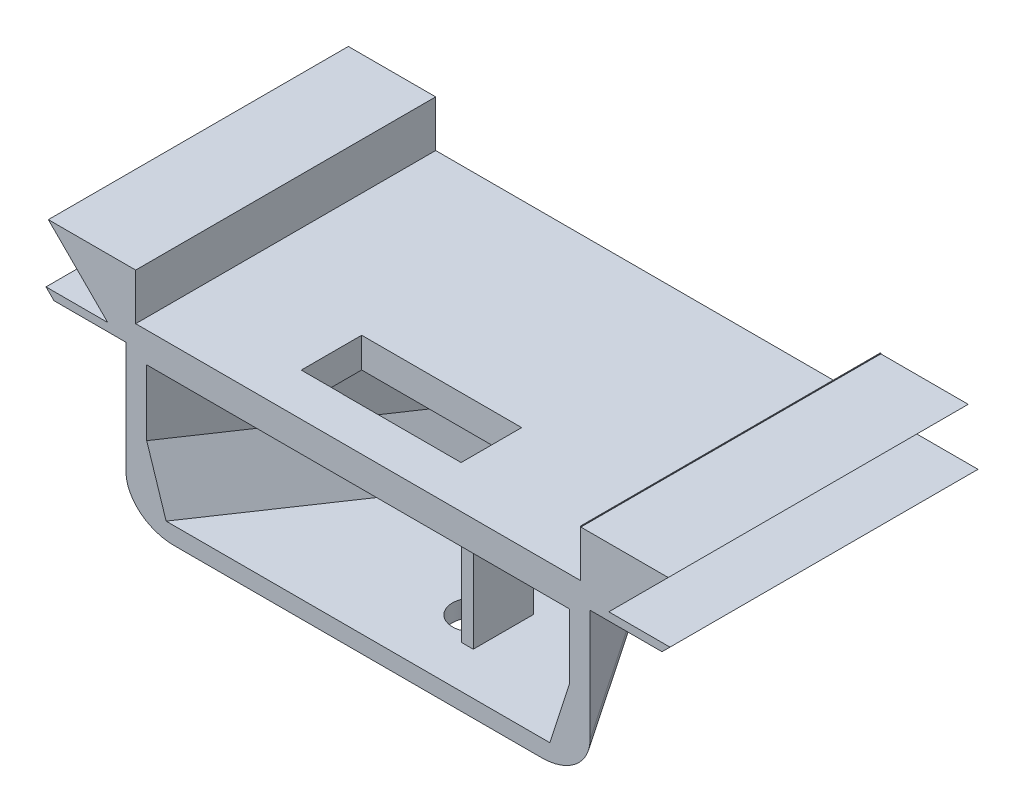
SolidWorks part; units mm, degrees
other "Camera1"
ref_plane "Front Plane" through (0, 0, 0) normal (0, 0, 1) x (1, 0, 0)
ref_plane "Top Plane" through (0, 0, 0) normal (0, 1, 0) x (1, 0, 0)
ref_plane "Right Plane" through (0, 0, 0) normal (1, 0, 0) x (0, 0, -1)
sketch "Sketch1" plane through (0, 0, 0) normal (0, 1, 0) x (1, 0, 0)
  line L0 (0, 0) -> (-116, 0)
  line L1 (-116, 0) -> (-75.5008, 60)
  line L2 (-75.5008, 60) -> (-40.5008, 60)
  line L3 (-40.5008, 60) -> (0, 0)
  dimension "D1" = 60
  dimension "D2" = 116
  dimension "D3" = 35
  dimension "D5" = 72.39
  dimension "D6" = 72.3891
extrude "Boss-Extrude1" add sketch "Sketch1" against normal blind 40
shell "Shell1" thickness 4.2918 removed face at (-58, -20, 0)
chamfer "Chamfer3" distance 15 angle 15 2 edges at (-92.0209, -35.7082, -27.8541) (-23.9799, -35.7082, -27.8541) first distance on face at (-92.0209, -20, -27.8541) first distance on face at (-23.9799, -20, -27.8541)
fillet "Fillet1" radius 10 2 edges at (-20.2504, -40, -30) (-95.7504, -40, -30)
fillet "Fillet2" radius 5 5 edges at (-40.5008, -15, -60) (-44.0345, -37.0711, -60) (-75.5008, -15, -60) (-71.9671, -37.0711, -60) (-58.0008, -40, -60)
sketch "Sketch12" plane through (0, -40, 0) normal (0, -1, 0) x (-1, 0, 0)
  circle A0 centre (47.2824, 18.1003) radius 5.2
sketch "Sketch13" plane through (0, -4.2918, 0) normal (0, -1, 0) x (1, 0, 0)
  line L1 (-39.8423, -25.7584) -> (-42.8423, -25.7584)
  line L2 (-39.8423, -25.7584) -> (-39.8423, -10.6584)
  line L3 (-39.8423, -10.6584) -> (-42.8423, -10.6584)
  line L4 (-42.8423, -25.7584) -> (-42.8423, -10.6584)
  dimension "D1" = 3
extrude "Boss-Extrude3" add sketch "Sketch13" along normal blind 35
extrude "Cut-Extrude12" cut sketch "Sketch12" against normal blind 9
sketch "Sketch15" plane through (0, 0, 0) normal (0, 1, 0) x (1, 0, 0)
  line L8 (-136, 75) -> (20, 75)
  line L9 (20, 0) -> (20, 75)
  line L10 (20, 0) -> (-136, 0)
  line L11 (-136, 0) -> (-136, 75)
extrude "Boss-Extrude7" add sketch "Sketch15" along normal blind 15
sketch "Sketch16" plane through (0, 0, 0) normal (0, 0, 1) x (1, 0, 0)
  line L1 (20.1, 15.2414) -> (20.1, -0.1)
  line L3 (20.1, -0.1) -> (4.7586, -0.1)
  line L6 (4.7586, -0.1) -> (20.1, 15.2414)
  line L8 (20, 15) -> (20, 0) construction
  line L9 (20, 0) -> (5, 0) construction
  line L10 (0, 0) -> (20, 0) construction
  line L11 (5, 0) -> (20, 15) construction
  dimension "D1" = 15
  dimension "D2" = 0.1
extrude "Cut-Extrude14" cut sketch "Sketch16" against normal blind 75
sketch "Sketch17" plane through (0, 0, 0) normal (0, 0, 1) x (1, 0, 0)
  line L0 (-136, 15) -> (-136, 0) construction
  line L1 (-136, 0) -> (-121, 0) construction
  line L2 (-136, 0) -> (-116, 0) construction
  line L3 (-121, 0) -> (-136, 15) construction
  line L4 (-120.5172, -0.2) -> (-136.2, 15.4828)
  line L5 (-136.2, 15.4828) -> (-136.2, -0.2)
  line L6 (-136.2, -0.2) -> (-120.5172, -0.2)
  dimension "D1" = 0.2
extrude "Cut-Extrude15" cut sketch "Sketch17" against normal blind 75
sketch "Sketch18" plane through (0, 0, 0) normal (0, -1, 0) x (1, 0, 0)
  line L0 (-116, 0) -> (-121, 0)
  line L1 (-121, 0) -> (-136.0045, 0)
  line L2 (-136.0045, 0) -> (-136.0045, -75)
  line L5 (20.0045, -75) -> (20.0045, 0)
  line L6 (20.0045, 0) -> (-116, 0)
  line L9 (-136.0045, -75) -> (-136.0045, -77)
  line L10 (20.0045, -75) -> (20.0045, -77)
  line L11 (20.0045, -77) -> (-136.0045, -77)
  dimension "D1" = 75
extrude "Boss-Extrude8" add sketch "Sketch18" along normal blind 2 contours L5 L6 L0 L1 L2 L9 L11 L10
sketch "Sketch20" plane through (0, -2, 0) normal (0, -1, 0) x (-1, 0, 0)
  line L1 (42.8423, 25.7218) -> (72.8207, 25.7218)
  line L2 (42.8423, 25.7218) -> (42.8423, 10.6218)
  line L3 (42.8423, 10.6218) -> (72.8207, 10.6218)
  line L4 (72.8207, 25.7218) -> (72.8207, 10.6218)
extrude "Cut-Extrude17" cut sketch "Sketch20" against normal blind 39 contours L2 L1 L4 L3
sketch "Sketch21" plane through (0, 0, 0) normal (0, 0, 1) x (1, 0, 0)
  line L6 (-135.7172, 15) -> (19.8586, 15) construction
  line L7 (-2.413, 15) -> (-113.583, 15)
  line L9 (-2.413, 15) -> (-113.583, 15)
  line L11 (-2.413, 15) -> (-2.413, 3.2309)
  line L12 (-2.413, 3.2309) -> (-113.583, 3.2309)
  line L13 (-113.583, 15) -> (-113.583, 3.2309)
extrude "Cut-Extrude18" cut sketch "Sketch21" against normal blind 80 contours L11 L9 L13 L12
sketch "Sketch22" plane through (-42.8423, 0, 0) normal (-1, 0, 0) x (0, 0, 1)
  line L1 (-10.6584, -35.7082) -> (-18.2084, -35.7082)
  line L2 (-10.6584, -35.7082) -> (-10.6584, -10.7935)
  line L3 (-10.6584, -10.7935) -> (-18.2084, -10.7935)
  line L4 (-18.2084, -35.7082) -> (-18.2084, -10.7935)
  circle A0 centre (-18.2084, -10.7935) radius 2.4
  dimension "D1" = 4.8
extrude "Cut-Extrude19" cut sketch "Sketch22" against normal blind 10 contours A0
sketch "Sketch27" plane through (0, -4.2918, 0) normal (0, -1, 0) x (-1, 0, 0)
  line L1 (42.8423, 10.6584) -> (82.8423, 10.6584)
  line L2 (42.8423, 10.6584) -> (42.8423, 25.7584)
  line L3 (42.8423, 25.7584) -> (82.8423, 25.7584)
  line L4 (82.8423, 10.6584) -> (82.8423, 25.7584)
extrude "Cut-Extrude24" cut sketch "Sketch27" against normal blind 19 contours L2 L1 L4 L3
sketch "Sketch28" plane through (0, 0, -55.7082) normal (0, 0, 1) x (1, 0, 0)
  line L1 (-53.7518, -25.9418) -> (-62.2518, -25.9418)
  line L2 (-53.7518, -25.9418) -> (-53.7518, -17.4418)
  line L3 (-53.7518, -17.4418) -> (-62.2518, -17.4418)
  line L4 (-62.2518, -25.9418) -> (-62.2518, -17.4418)
  line L10 (-42.7818, -20.7082) -> (-42.7818, -4.2918) construction
  line L12 (-42.7818, -4.2918) -> (-73.2197, -4.2918) construction
  dimension "D1" = 10.97
  dimension "D2" = 13.15
sketch "Sketch30" plane through (0, 0, -55.7082) normal (0, 0, 1) x (1, 0, 0)
  line L0 (-62.2518, -25.9418) -> (-62.2518, -17.4418) construction
  line L1 (-42.7818, -4.2918) -> (-73.2197, -4.2918) construction
  circle A0 centre (-68.5018, -21.7918) radius 1.1 construction
  circle A1 centre (-68.5018, -21.7918) radius 1.35
  dimension "D1" = 6.25
  dimension "D2" = 17.5
  dimension "D3" = 0.25
sketch "Sketch31" plane through (0, 0, -55.7082) normal (0, 0, 1) x (1, 0, 0)
  line L0 (-42.7818, -4.2918) -> (-73.2197, -4.2918) construction
  line L1 (-62.2518, -25.9418) -> (-62.2518, -17.4418) construction
  circle A0 centre (-68.5018, -9.2918) radius 1.1 construction
  circle A1 centre (-68.5018, -9.2918) radius 1.35
  dimension "D1" = 5
  dimension "D2" = 6.25
  dimension "D3" = 0.25
extrude "Cut-Extrude25" cut sketch "Sketch28" against normal blind 10
extrude "Cut-Extrude26" cut sketch "Sketch30" against normal blind 10
extrude "Cut-Extrude27" cut sketch "Sketch31" against normal blind 10
sketch "Sketch32" plane through (0, 0, -55.7082) normal (0, 0, 1) x (1, 0, 0)
  line L0 (-53.7518, -25.9418) -> (-53.7518, -17.4418) construction
  line L1 (-42.7818, -4.2918) -> (-73.2197, -4.2918) construction
  circle A0 centre (-47.5018, -21.7918) radius 1.1 construction
  circle A1 centre (-47.5018, -9.2918) radius 1.1 construction
  circle A2 centre (-47.5018, -21.7918) radius 1.35
  circle A3 centre (-47.5018, -9.2918) radius 1.35
  dimension "D1" = 6.25
  dimension "D2" = 17.5
  dimension "D3" = 5
  dimension "D4" = 6.25
  dimension "D5" = 0.25
  dimension "D6" = 0.25
extrude "Cut-Extrude29" cut sketch "Sketch32" against normal blind 10
sketch "Sketch34" plane through (0, 0, 0) normal (0, 0, 1) x (1, 0, 0)
  line L0 (-120.7172, 0) -> (-120.5672, 0) construction
  line L2 (-120.5672, 0) -> (-120.5672, 14.85) construction
  line L3 (-120.7172, 0) -> (-120.5672, 0)
  line L4 (-120.5672, 0) -> (-135.4172, 14.85)
  line L6 (-120.5672, 14.85) -> (-113.583, 14.85)
  line L7 (-113.583, 15) -> (-113.583, 3.2309) construction
  line L8 (-120.5672, 14.85) -> (-135.4172, 14.85)
  line L9 (-113.583, 14.85) -> (-113.583, 15)
  line L10 (-113.583, 15) -> (-135.7172, 15)
  line L11 (-135.7172, 15) -> (-120.7172, 0)
  line L12 (-120.7172, 0) -> (4.8586, 0) construction
  line L14 (-57.9293, 0) -> (-57.9293, 31.8662) construction
  line L15 (-2.2756, 15) -> (19.8586, 15)
  line L16 (-2.2756, 14.85) -> (-2.2756, 15)
  line L17 (4.7086, 14.85) -> (-2.2756, 14.85)
  line L18 (4.7086, 14.85) -> (19.5586, 14.85)
  line L19 (4.7086, 0) -> (19.5586, 14.85)
  line L20 (4.8586, 0) -> (4.7086, 0)
  line L21 (19.8586, 15) -> (4.8586, 0)
  dimension "D1" = 0.15
  dimension "D2" = 14.85
  dimension "D3" = 45
extrude "Cut-Extrude30" cut sketch "Sketch34" against normal through all
chamfer "Chamfer4" distance 2 angle 45 3 edges at (20.0045, -2, -38.5) (-58, -2, -77) (-136.0045, -2, -38.5)
sketch "Sketch35" plane through (0, 0, 0) normal (0, 0, 1) x (1, 0, 0)
  line L0 (-120.5672, 0) -> (-120.5672, 14.85) construction
  line L1 (-135.4172, 14.85) -> (-113.583, 14.85) construction
  line L2 (-120.5672, 14.85) -> (-135.4172, 14.85) construction
  line L3 (4.7086, 0) -> (4.7086, 14.85) construction
  line L4 (-2.2756, 14.85) -> (19.5586, 14.85) construction
  line L5 (4.7086, 14.85) -> (19.5586, 14.85) construction
